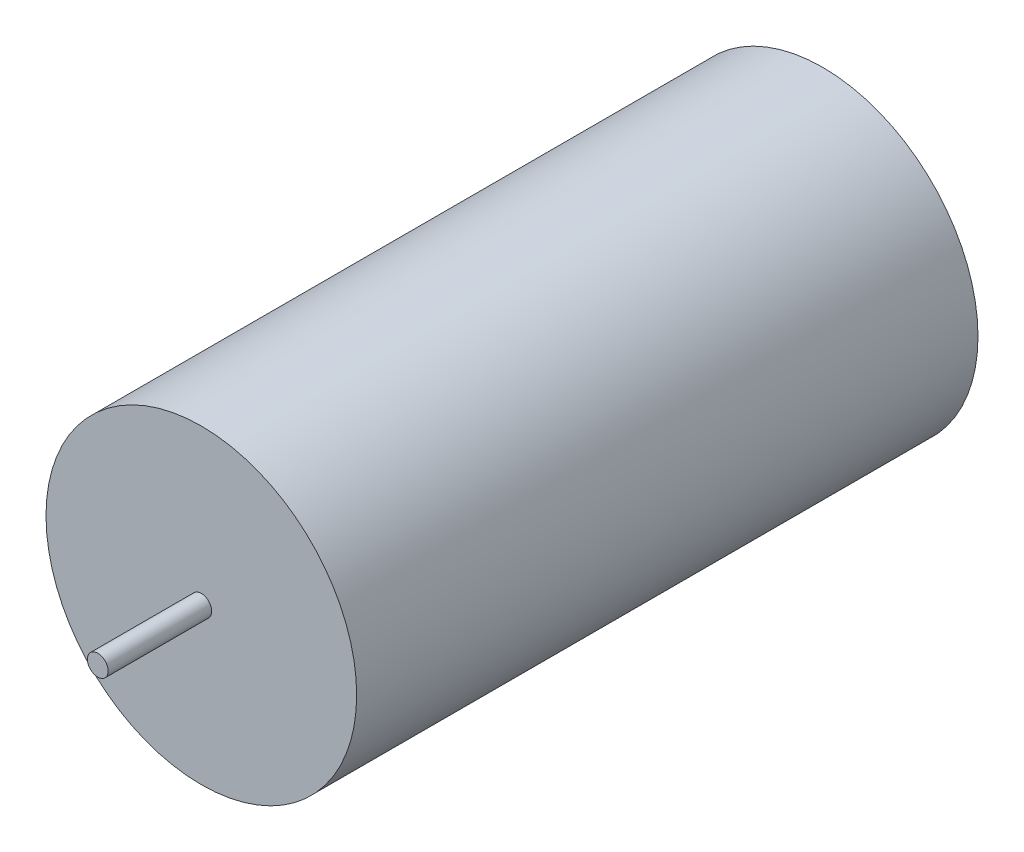
SolidWorks part; units mm, degrees
material "1023 Carbon Steel Sheet (SS)"
ref_plane "Front Plane" through (0, 0, 0) normal (0, 0, 1) x (1, 0, 0)
ref_plane "Top Plane" through (0, 0, 0) normal (0, 1, 0) x (1, 0, 0)
ref_plane "Right Plane" through (0, 0, 0) normal (1, 0, 0) x (0, 0, -1)
sketch "Sketch1" plane through (0, 0, 0) normal (0, 0, 1) x (1, 0, 0)
  circle A0 centre (0, -25.4) radius 19.05
extrude "Boss-Extrude1" add sketch "Sketch1" against normal blind 76.2
sketch "Sketch2" plane through (0, 0, 0) normal (0, 0, 1) x (1, 0, 0)
  circle A0 centre (0, -25.4) radius 1.27
  dimension "D1" = 2.54
extrude "Boss-Extrude2" add sketch "Sketch2" along normal blind 12.7
